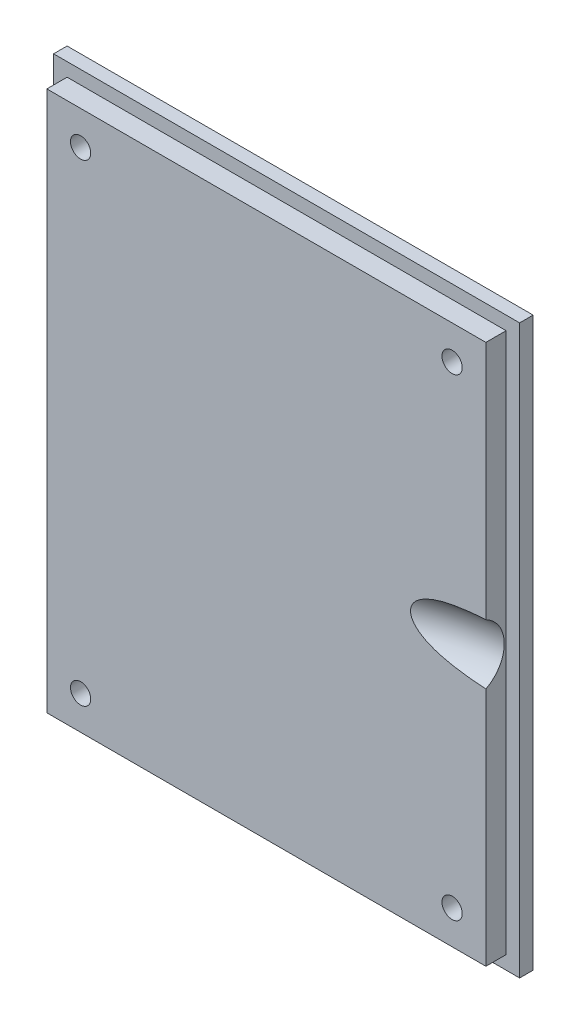
SolidWorks part; units mm, degrees
ref_plane "前视基准面" through (0, 0, 0) normal (0, 0, 1) x (1, 0, 0)
ref_plane "上视基准面" through (0, 0, 0) normal (0, 1, 0) x (1, 0, 0)
ref_plane "右视基准面" through (0, 0, 0) normal (1, 0, 0) x (0, 0, -1)
sketch "草图1" plane through (0, 0, 0) normal (0, 0, 1) x (1, 0, 0)
  line L0 (-32.5, -40) -> (-32.5, 40)
  line L1 (-37.5, -45) -> (37.5, -45)
  line L2 (-37.5, -45) -> (-37.5, 45)
  line L3 (-37.5, 45) -> (37.5, 45)
  line L4 (37.5, -45) -> (37.5, 45)
  line L5 (-37.5, -45) -> (37.5, 45) construction
  line L6 (-37.5, 45) -> (37.5, -45) construction
  line L7 (-32.5, 40) -> (32.5, 40)
  line L8 (32.5, -40) -> (32.5, 40)
  line L9 (-32.5, -40) -> (32.5, -40)
  line L10 (-34.5, -42) -> (-34.5, 42)
  line L11 (-34.5, 42) -> (34.5, 42)
  line L12 (34.5, -42) -> (34.5, 42)
  line L13 (-34.5, -42) -> (34.5, -42)
  point P0 (0, 0)
  point P14 (0, 0)
  dimension "D1" = 75
  dimension "D2" = 90
  dimension "D3" = 5
  dimension "D4" = 2
extrude "凸台-拉伸1" add sketch "草图1" along normal blind 5 contours L0 L7 L8 L9
extrude "凸台-拉伸2" add sketch "草图1<3>" along normal blind 2 contours L10 L13 L12 L11 L9 L0 L7 L8 region at (-33.4129, 0, 0)
sketch "草图1<3>" plane through (0, 0, 0) normal (0, 0, 1) x (1, 0, 0) same geometry as "草图1"
sketch "草图3" plane through (0, 0, 0) normal (0, 1, 0) x (1, 0, 0)
  line L1 (37.5, 0) -> (37.5, -4.1568) construction
  line L4 (-37.5, 0) -> (37.5, 0) construction
  arc A0 (37.5, -7) -> (17.5, -12.359) centre (37.5, -47) ccw
  point P3 (0, 0)
  point P5 (37.5, -42.425)
  dimension "D1" = 40
  dimension "D2" = 7
  dimension "D3" = 30
sweep "切除-扫描1" cut path "草图3" circular profile diameter 10 parameters "D3"=10
sketch "草图8" plane through (0, 0, 0) normal (0, 0, -1) x (-1, 0, 0)
  line L0 (0, 0) -> (0, 18.9134) construction
  line L1 (-66.3937, 0) -> (-56.848, 0) construction
  line L2 (37.5, 45) -> (-37.5, 45) construction
  line L3 (-37.5, -45) -> (-37.5, 45) construction
  circle A0 centre (-27.5, 35) radius 1.5
  circle A1 centre (27.5, 35) radius 1.5
  circle A2 centre (27.5, -35) radius 1.5
  circle A3 centre (-27.5, -35) radius 1.5
  dimension "D1" = 3
  dimension "D2" = 10
  dimension "D3" = 10
extrude "切除-拉伸1" cut sketch "草图8" against normal through all
